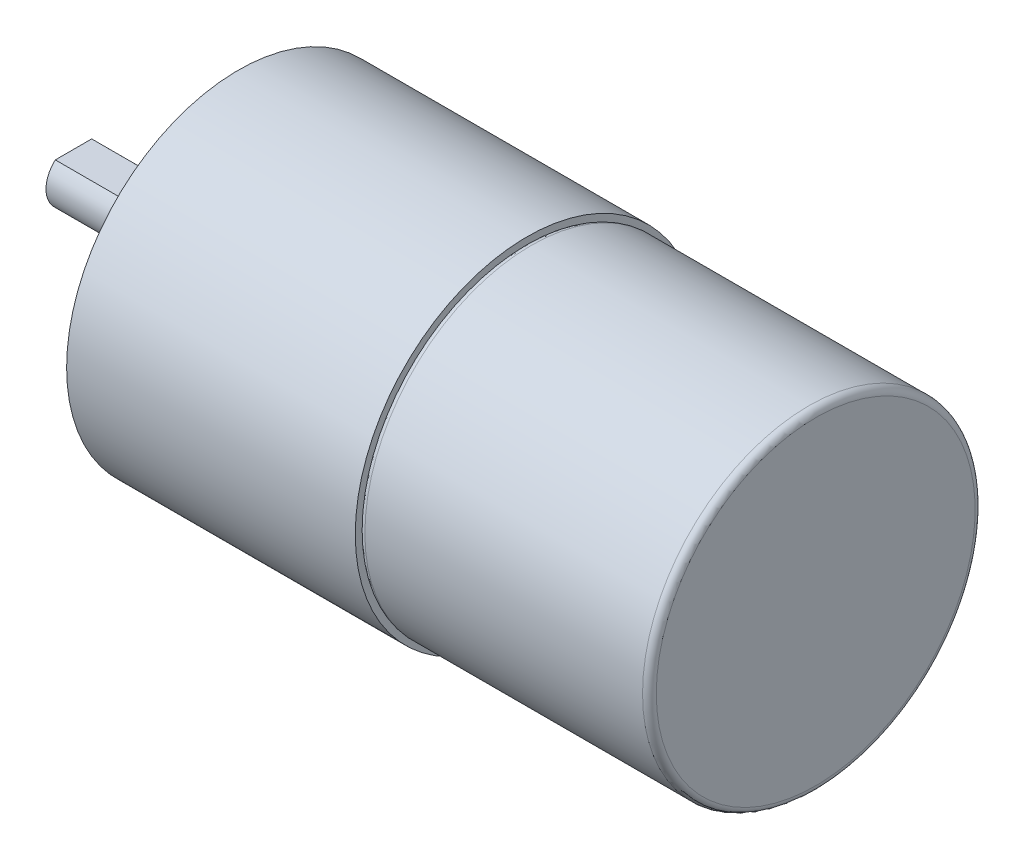
SolidWorks part; units mm, degrees
material "AISI 304"
ref_plane "Front Plane" through (0, 0, 0) normal (0, 0, 1) x (1, 0, 0)
ref_plane "Top Plane" through (0, 0, 0) normal (0, 1, 0) x (1, 0, 0)
ref_plane "Right Plane" through (0, 0, 0) normal (1, 0, 0) x (0, 0, -1)
sketch "Sketch1" plane through (0, 0, 0) normal (0, 0, 1) x (1, 0, 0)
  line L0 (-27, 0) -> (27, 0)
  line L1 (-27, 0) -> (-27, 2)
  line L2 (-27, 2) -> (-17.5, 2)
  line L3 (-17.5, 2) -> (-17.5, 3.5)
  line L4 (-17.5, 3.5) -> (-15, 3.5)
  line L5 (-15, 3.5) -> (-15, 12.5)
  line L6 (-15, 12.5) -> (6, 12.5)
  line L7 (6, 12.5) -> (6, 12)
  line L8 (6, 12) -> (6.1, 12.1)
  line L9 (6.1, 12.1) -> (27, 12.1)
  line L10 (27, 12.1) -> (27, 0)
  point P4 (0, 0)
  dimension "D1" = 54
  dimension "D2" = 2
  dimension "D3" = 9.5
  dimension "D4" = 12
  dimension "D5" = 3.5
  dimension "D6" = 12.5
  dimension "D7" = 12.1
  dimension "D8" = 21
  dimension "D9" = 45
  dimension "D10" = 0.5
revolve "Revolve1" add sketch "Sketch1" angle 360 about L0
fillet "Fillet1" radius 0.5 2 edges at (27, 0, 12.1) (6.1, 0, 12.1)
sketch "Sketch2" plane through (0, 0, 0) normal (0, 0, 1) x (1, 0, 0)
  line L1 (-27, 2) -> (-19, 2)
  line L2 (-27, 2) -> (-27, 1.5)
  line L3 (-27, 1.5) -> (-19, 1.5)
  line L4 (-19, 2) -> (-19, 1.5)
  dimension "D1" = 0.5
  dimension "D2" = 8
extrude "Cut-Extrude1" cut sketch "Sketch2" against normal mid plane 10
sketch "Sketch3" plane through (-15, 0, 0) normal (-1, 0, 0) x (0, 0, 1)
  circle A0 centre (0, 0) radius 8.5 construction
  circle A1 centre (0, 8.5) radius 1.5
  circle A2 centre (0, -8.5) radius 1.5
  dimension "D1" = 17
  dimension "D2" = 3
extrude "Cut-Extrude2" cut sketch "Sketch3" against normal blind 5
